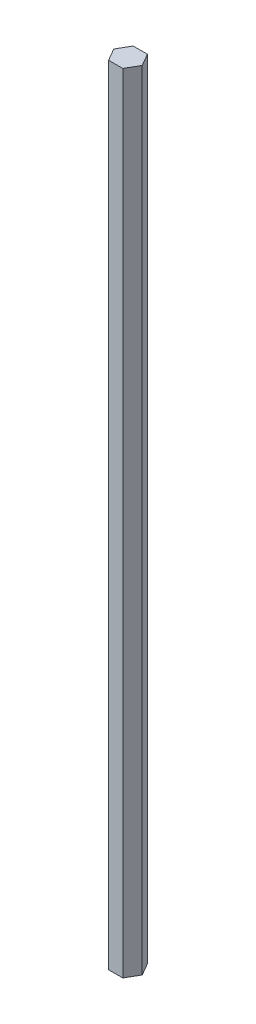
SolidWorks part; units mm, degrees
ref_plane "Front Plane" through (0, 0, 0) normal (0, 0, 1) x (1, 0, 0)
ref_plane "Top Plane" through (0, 0, 0) normal (0, 1, 0) x (1, 0, 0)
ref_plane "Right Plane" through (0, 0, 0) normal (1, 0, 0) x (0, 0, -1)
sketch "Sketch1" plane through (0, 0, 0) normal (0, 1, 0) x (1, 0, 0)
  line L7 (7.3323, 0) -> (3.6662, 6.35)
  line L8 (3.6662, 6.35) -> (-3.6662, 6.35)
  line L9 (-3.6662, 6.35) -> (-7.3323, 0)
  line L10 (-7.3323, 0) -> (-3.6662, -6.35)
  line L11 (-3.6662, -6.35) -> (3.6662, -6.35)
  line L12 (3.6662, -6.35) -> (7.3323, 0)
  circle A0 centre (0, 0) radius 6.35 construction
  dimension "D1" = 12.7
extrude "Boss-Extrude1" add sketch "Sketch1" along normal mid plane 406.4
ref_axis "Axis1" through (0, 273.0375, 0) along (0, -1, 0)
